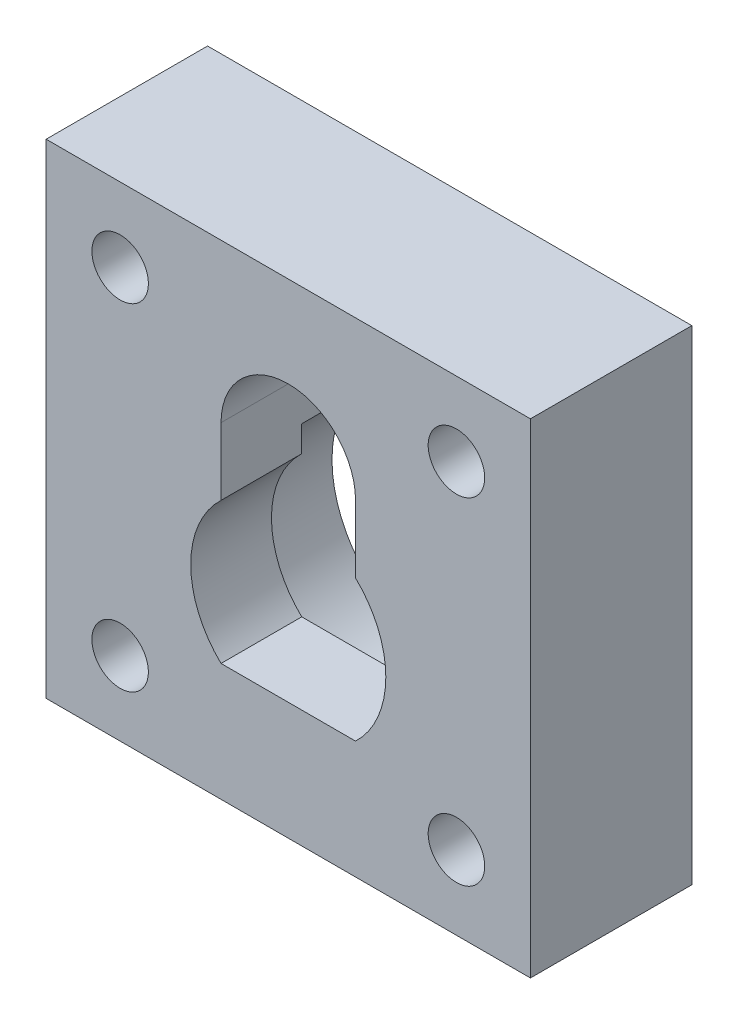
SolidWorks part; units mm, degrees
ref_plane "Front Plane" through (0, 0, 0) normal (0, 0, 1) x (1, 0, 0)
ref_plane "Top Plane" through (0, 0, 0) normal (0, 1, 0) x (1, 0, 0)
ref_plane "Right Plane" through (0, 0, 0) normal (1, 0, 0) x (0, 0, -1)
sketch "Sketch1" plane through (0, 0, 0) normal (0, 0, 1) x (1, 0, 0)
  line L1 (18, -18) -> (-18, -18)
  line L2 (18, -18) -> (18, 18)
  line L3 (18, 18) -> (-18, 18)
  line L4 (-18, -18) -> (-18, 18)
  line L5 (18, -18) -> (-18, 18) construction
  line L6 (18, 18) -> (-18, -18) construction
  point P0 (0, 0)
  dimension "D1" = 36
  dimension "D2" = 36
extrude "Boss-Extrude1" add sketch "Sketch1" along normal blind 12
sketch "Sketch2" plane through (0, 0, 0) normal (0, 0, -1) x (-1, 0, 0)
  line L1 (18, -18) -> (-18, -18) construction
  line L3 (18, 18) -> (18, -18) construction
  circle A0 centre (0, -4) radius 8.75
  dimension "D1" = 17.5
  dimension "D3" = 5.25
  dimension "D4" = 9.25
  dimension "D2" = 4
extrude "Cut-Extrude1" cut sketch "Sketch2" against normal blind 6
sketch "Sketch3" plane through (0, 0, 6) normal (0, 0, -1) x (-1, 0, 0)
  line L0 (-5, 1.25) -> (5, 1.25)
  line L1 (-5, -9.25) -> (5, -9.25)
  line L2 (-7.25, -4) -> (7.25, -4) construction
  arc A0 (-5, 1.25) -> (-5, -9.25) centre (0, -4) ccw
  circle A1 centre (0, -4) radius 8.75 construction
  arc A2 (5, -9.25) -> (5, 1.25) centre (0, -4) ccw
  dimension "D1" = 14.5
  dimension "D2" = 10.5
extrude "Cut-Extrude2" cut sketch "Sketch3" against normal up to next
sketch "Sketch4" plane through (0, 0, 0) normal (0, 0, -1) x (-1, 0, 0)
  line L0 (5, 1.25) -> (-5, 1.25) construction
  line L1 (-5, 6.25) -> (-5, 1.25)
  line L2 (5, 6.25) -> (5, 1.25)
  line L3 (-5, 1.25) -> (5, 1.25)
  arc A0 (5, 6.25) -> (-5, 6.25) centre (0, 6.25) ccw
  dimension "D1" = 10
extrude "Cut-Extrude3" cut sketch "Sketch4" against normal up to next
hole_wizard "M5x0.8 Tapped Hole1" positions "Sketch7" profile "Sketch6" tap size "M5x0.8" standard "ANSI Metric" end condition through all
sketch "Sketch7" plane through (0, 0, 12) normal (0, 0, 1) x (1, 0, 0)
  line L0 (-12.5, 12.5) -> (12.5, 12.5) construction
  line L1 (12.5, 12.5) -> (12.5, -12.5) construction
  point P0 (-12.5, -12.5)
  point P2 (12.5, -12.5)
  point P4 (12.5, 12.5)
  point P6 (-12.5, 12.5)
  point P13 (0, 12.5)
  point P15 (12.5, 0)
  dimension "D1" = 25
  dimension "D2" = 25
sketch "Sketch6" plane through (-12.5, -12.5, 12) normal (1, 0, 0) x (0, -1, 0)
  line L0 (0, 0) -> (0, 12)
  line L1 (0, 12) -> (2.1, 12)
  line L2 (2.1, 12) -> (2.1, 0)
  line L5 (2.1, 0) -> (0, 0)
  line L11 (0, -6.35) -> (0, 107.95) construction
  dimension "Thru Tap Drill Dia." = 4.2
  dimension "Thru Tap Drill Depth" = 12
